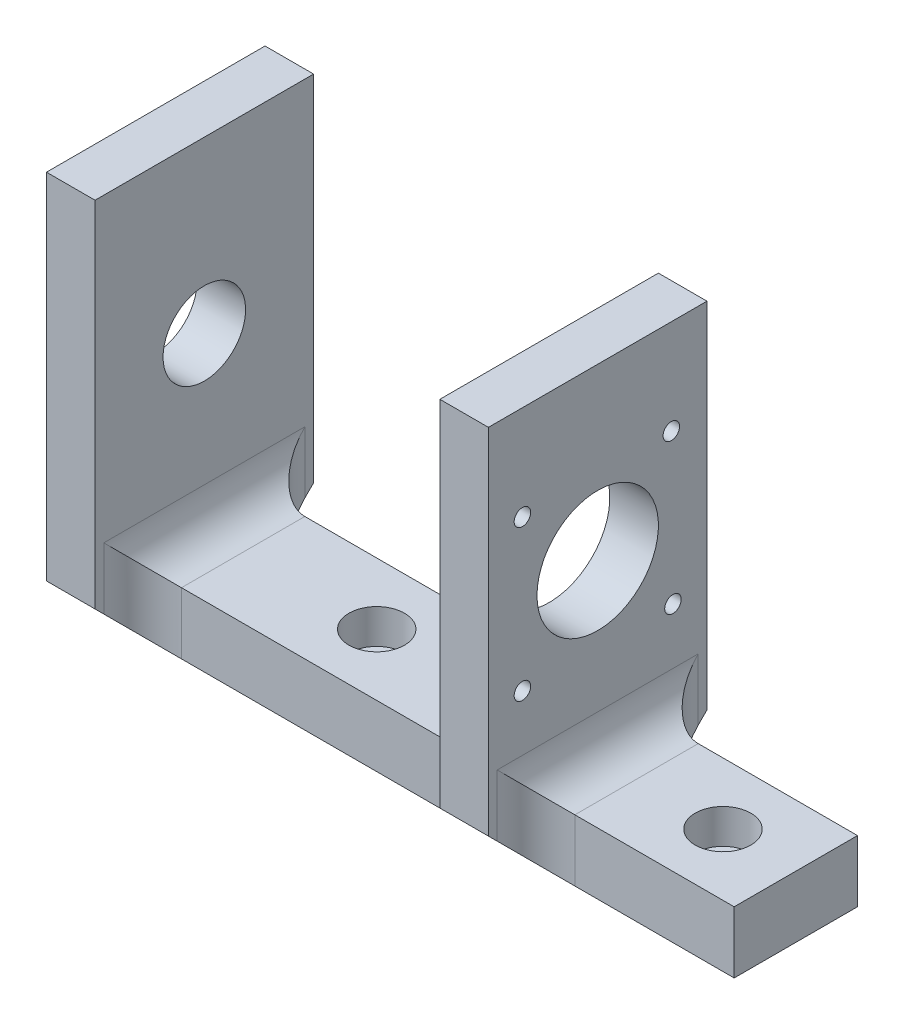
SolidWorks part; units mm, degrees
ref_plane "Front Plane" through (0, 0, 0) normal (0, 0, 1) x (1, 0, 0)
ref_plane "Top Plane" through (0, 0, 0) normal (0, 1, 0) x (1, 0, 0)
ref_plane "Right Plane" through (0, 0, 0) normal (1, 0, 0) x (0, 0, -1)
sketch "Sketch1" plane through (0, 0, 0) normal (0, 1, 0) x (1, 0, 0)
  line L1 (-25.4, -12.7) -> (25.4, -12.7)
  line L2 (-25.4, -12.7) -> (-25.4, 12.7)
  line L3 (-25.4, 12.7) -> (25.4, 12.7)
  line L4 (25.4, -12.7) -> (25.4, 12.7)
  line L5 (-25.4, -12.7) -> (25.4, 12.7) construction
  line L6 (-25.4, 12.7) -> (25.4, -12.7) construction
  point P0 (0, 0)
  dimension "D1" = 25.4
  dimension "D2" = 50.8
extrude "Boss-Extrude1" add sketch "Sketch1" along normal blind 12.7
sketch "Sketch2" plane through (-25.4, 0, 0) normal (-1, 0, 0) x (0, 0, 1)
  line L1 (-15.5, 32.2) -> (15.5, 32.2) construction
  line L2 (-15.5, 32.2) -> (-15.5, 63.2) construction
  line L3 (-15.5, 63.2) -> (15.5, 63.2) construction
  line L4 (15.5, 32.2) -> (15.5, 63.2) construction
  line L5 (-15.5, 32.2) -> (15.5, 63.2) construction
  line L6 (-15.5, 63.2) -> (15.5, 32.2) construction
  line L7 (-12.7, 12.7) -> (12.7, 12.7) construction
  line L8 (-22.5, 12.7) -> (22.5, 12.7)
  line L9 (-22.5, 12.7) -> (-22.5, 82.7)
  line L10 (-22.5, 82.7) -> (22.5, 82.7)
  line L11 (22.5, 12.7) -> (22.5, 82.7)
  line L12 (-22.5, 12.7) -> (22.5, 82.7) construction
  line L13 (-22.5, 82.7) -> (22.5, 12.7) construction
  circle A0 centre (0, 47.7) radius 12.5
  point P0 (0, 47.7)
  point P5 (0, 47.7)
  point P15 (0, 0)
  point P16 (0, 0)
  dimension "D3" = 25
  dimension "D1" = 31
  dimension "D2" = 70
  dimension "D4" = 45
extrude "Boss-Extrude2" add sketch "Sketch2" against normal blind 10
chamfer "Chamfer1" distance 12.7 angle 45 2 edges at (-20.4, 12.7, 12.7) (-20.4, 12.7, -12.7)
hole_wizard "M3 Clearance Hole1" positions "Sketch3" profile "Sketch4" hole size "M3" standard "ANSI Metric" end condition through all
sketch "Sketch3" plane through (-25.4, 0, 0) normal (-1, 0, 0) x (0, 0, 1)
  line L0 (-15.5, 63.2) -> (15.5, 63.2) construction
  point P0 (-15.1608, 63.2)
  point P4 (15.5, 63.2)
  point P7 (15.5, 32.2)
  point P10 (-15.5, 32.2)
sketch "Sketch4" plane through (-25.4, 63.2, -15.1608) normal (0, 1, 0) x (0, 0, 1)
  line L0 (0, 0) -> (0, 50.8)
  line L1 (0, 50.8) -> (1.7, 50.8)
  line L2 (1.7, 50.8) -> (1.7, 0)
  line L5 (1.7, 0) -> (0, 0)
  line L11 (0, -6.35) -> (0, 107.95) construction
  dimension "Thru Hole Dia." = 3.4
  dimension "Thru Hole Depth" = 50.8
sketch "Sketch5" plane through (0, 12.7, 0) normal (0, 1, 0) x (1, 0, 0)
  line L0 (25.4, 0) -> (-15.4, 0) construction
  line L1 (25.4, -12.7) -> (25.4, 12.7) construction
  line L2 (-15.4, -22.5) -> (-15.4, 22.5) construction
  point P6 (10.4, 0)
  point P8 (0, 0)
  dimension "D1" = 15
hole_wizard "1/4 Clearance Hole1" positions "Sketch6" profile "Sketch7" hole size "1/4" standard "ANSI Inch" end condition through all
sketch "Sketch6" plane through (0, 12.7, 0) normal (0, 1, 0) x (1, 0, 0)
  point P3 (10.4, 0)
  point P6 (0, 0)
sketch "Sketch7" plane through (10.4, 12.7, 0) normal (1, 0, 0) x (0, 0, 1)
  line L0 (0, 0) -> (0, 12.7)
  line L1 (0, 12.7) -> (3.3782, 12.7)
  line L2 (3.3782, 12.7) -> (3.3782, 0)
  line L5 (3.3782, 0) -> (0, 0)
  line L11 (0, -6.35) -> (0, 107.95) construction
  dimension "Thru Hole Dia." = 6.7564
  dimension "Thru Hole Depth" = 12.7
sketch "Sketch8" plane through (0, 12.7, 0) normal (0, 1, 0) x (1, 0, 0)
  circle A1 centre (10.4, 0) radius 5.715
  dimension "D1" = 11.43
extrude "Cut-Extrude1" cut sketch "Sketch8" against normal blind 7.112
sketch "Sketch9" plane through (-25.4, 0, 0) normal (-1, 0, 0) x (0, 0, 1)
  line L0 (-12.7, 0) -> (12.7, 0) construction
  line L1 (-12.7, 12.7) -> (12.7, 12.7)
  line L2 (-12.7, 12.7) -> (-12.7, 0)
  line L3 (-12.7, 0) -> (12.7, 0)
  line L4 (12.7, 12.7) -> (12.7, 0)
  point P6 (0, 0)
  dimension "D1" = 25.4
  dimension "D2" = 12.7
extrude "Boss-Extrude3" add sketch "Sketch9" along normal blind 71
sketch "Sketch11" plane through (-96.4, 0, 0) normal (-1, 0, 0) x (0, 0, 1)
  line L0 (-12.7, 0) -> (12.7, 0) construction
  line L1 (-12.7, 0) -> (12.7, 0)
  line L8 (-12.7, 0) -> (-12.7, 12.7)
  line L9 (-12.7, 12.7) -> (12.7, 12.7)
  line L10 (12.7, 12.7) -> (12.7, 0)
  line L11 (12.7, 0) -> (22.5, 9.8)
  line L12 (22.5, 9.8) -> (22.5, 82.7)
  line L13 (22.5, 82.7) -> (-22.5, 82.7)
  line L14 (-22.5, 82.7) -> (-22.5, 9.8)
  line L15 (-22.5, 9.8) -> (-12.7, 0)
  line L19 (12.7, 0) -> (22.5, 9.8)
  line L20 (22.5, 9.8) -> (22.5, 82.7)
  line L21 (22.5, 82.7) -> (-22.5, 82.7)
  line L22 (-22.5, 82.7) -> (-22.5, 9.8)
  line L23 (-22.5, 9.8) -> (-12.7, 0)
  dimension "D1" = 0
extrude "Boss-Extrude4" add sketch "Sketch11" along normal blind 10
sketch "Sketch12" plane through (-106.4, 0, 0) normal (-1, 0, 0) x (0, 0, 1)
  line L0 (-15.5, 32.2) -> (15.5, 63.2) construction
  circle A0 centre (0, 47.7) radius 8.5
  dimension "D1" = 17
extrude "Cut-Extrude2" cut sketch "Sketch12" against normal up to next
sketch "Sketch13" plane through (0, 12.7, 0) normal (0, 1, 0) x (1, 0, 0)
  line L0 (-96.4, 0) -> (-25.4, 0) construction
  line L1 (-96.4, -12.7) -> (-96.4, 12.7) construction
  line L2 (-25.4, 22.5) -> (-25.4, -22.5) construction
  point P6 (-60.9, 0)
sketch "Sketch14" plane through (0, 12.7, 0) normal (0, 1, 0) x (1, 0, 0)
  line L0 (-96.4, 0) -> (-25.4, 0) construction
  circle A0 centre (-60.9, 0) radius 5.715
  dimension "D1" = 11.43
extrude "Cut-Extrude3" cut sketch "Sketch14" against normal blind 7.11
sketch "Sketch15" plane through (0, 5.59, 0) normal (0, 1, 0) x (1, 0, 0)
  line L0 (-96.4, 0) -> (-25.4, 0) construction
  circle A0 centre (-60.9, 0) radius 3.38
  dimension "D1" = 6.76
extrude "Cut-Extrude4" cut sketch "Sketch15" against normal through all
fillet "Fillet2" radius 8 6 edges at (-15.4, 6.35, -12.7) (-25.4, 6.35, -12.7) (-96.4, 6.35, -12.7) (-96.4, 6.35, 12.7) (-15.4, 6.35, 12.7) (-25.4, 6.35, 12.7)
fillet "Fillet1" radius 8 3 edges at (-96.4, 12.7, 0) (-25.4, 12.7, 0) (-15.4, 12.7, 0)
